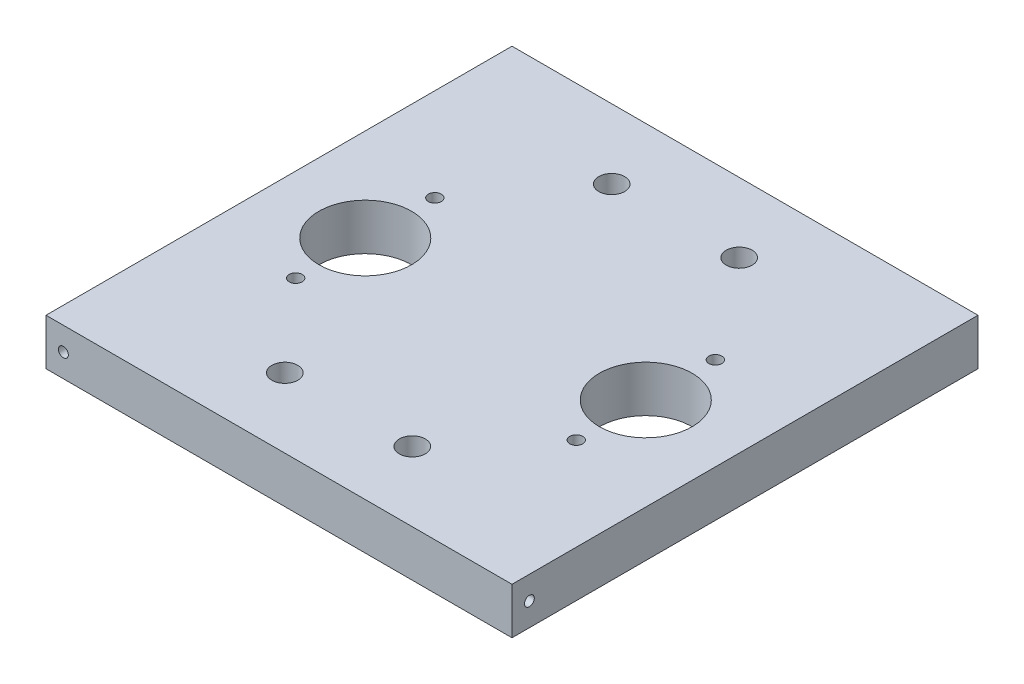
SolidWorks part; units mm, degrees
material "6061-T6 (SS)"
ref_plane "Front" through (0, 0, 0) normal (0, 0, 1) x (1, 0, 0)
ref_plane "Top" through (0, 0, 0) normal (0, 1, 0) x (1, 0, 0)
ref_plane "Right" through (0, 0, 0) normal (1, 0, 0) x (0, 0, -1)
sketch "Sketch1" plane through (0, 0, 0) normal (0, 1, 0) x (1, 0, 0)
  line L1 (0, 0) -> (127.635, 0)
  line L2 (0, 0) -> (0, 127.635)
  line L3 (0, 127.635) -> (127.635, 127.635)
  line L4 (127.635, 0) -> (127.635, 127.635)
  dimension "D1" = 127.635
  dimension "D2" = 127.635
extrude "Main Plate" add sketch "Sketch1" along normal blind 12.7
sketch "Sketch2" plane through (0, 12.7, 0) normal (0, 1, 0) x (1, 0, 0)
  line L0 (0, 127.635) -> (0, 0) construction
  line L1 (127.635, 127.635) -> (0, 127.635) construction
  circle A0 centre (46.355, 108.585) radius 3.556
  dimension "D1" = 7.112
  dimension "D2" = 46.355
  dimension "D3" = 19.05
extrude "U-Bolt Hole" cut sketch "Sketch2" against normal blind 12.7
pattern_linear "U-Bolt Pattern" count 2 spacing 34.925 along (1, 0, 0) count 2 spacing 89.535 along (0, 0, 1) of "U-Bolt Hole"
sketch "Sketch3" plane through (0, 12.7, 0) normal (0, 1, 0) x (1, 0, 0)
  line L0 (0, 127.635) -> (0, 0) construction
  line L1 (0, 0) -> (127.635, 0) construction
  circle A0 centre (25.4, 42.9895) radius 1.778
  dimension "D1" = 3.556
  dimension "D2" = 25.4
  dimension "D3" = 42.9895
extrude "Raptor Bolt Hole" cut sketch "Sketch3" against normal blind 12.7
pattern_linear "Raptor Bolt Pattern" count 2 spacing 38.1 along (0, 0, -1) count 2 spacing 76.835 along (1, 0, 0) of "Raptor Bolt Hole"
sketch "Sketch4" plane through (0, 12.7, 0) normal (0, 1, 0) x (1, 0, 0)
  line L0 (0, 127.635) -> (0, 0) construction
  circle A0 centre (25.4, 62.0395) radius 12.7
  dimension "D1" = 25.4
  dimension "D2" = 19.05
  dimension "D3" = 25.4
extrude "Co2 Cylinder Hole" cut sketch "Sketch4" against normal blind 12.7
pattern_linear "Co2 Pattern" count 2 spacing 76.835 along (1, 0, 0) of "Co2 Cylinder Hole"
sketch "Sketch5" plane through (0, 0, 0) normal (0, 0, 1) x (1, 0, 0)
  line L0 (0, 12.7) -> (0, 0) construction
  line L1 (0, 0) -> (127.635, 0) construction
  circle A0 centre (4.7625, 6.35) radius 1.3526
  dimension "D1" = 2.7051
  dimension "D2" = 4.7625
  dimension "D3" = 6.35
extrude "Frame attachment hole 1" cut sketch "Sketch5" against normal blind 12.7
sketch "Sketch6" plane through (0, 0, 0) normal (-1, 0, 0) x (0, 0, 1)
  line L2 (-127.635, 0) -> (0, 0) construction
  line L3 (-127.635, 12.7) -> (-127.635, 0) construction
  circle A0 centre (-122.8725, 6.35) radius 1.3525
  dimension "D1" = 2.7051
  dimension "D2" = 6.35
  dimension "D3" = 4.7625
extrude "Frame attachment hole 2" cut sketch "Sketch6" against normal blind 12.7
sketch "Sketch7" plane through (0, 0, -127.635) normal (0, 0, -1) x (-1, 0, 0)
  line L2 (-127.635, 0) -> (0, 0) construction
  line L3 (-127.635, 12.7) -> (-127.635, 0) construction
  circle A0 centre (-122.8725, 6.35) radius 1.3525
  dimension "D1" = 2.7051
  dimension "D2" = 6.35
  dimension "D3" = 4.7625
extrude "Frame attachment hole 3" cut sketch "Sketch7" against normal blind 12.7
sketch "Sketch8" plane through (127.635, 0, 0) normal (1, 0, 0) x (0, 0, -1)
  line L2 (0, 0) -> (127.635, 0) construction
  line L3 (0, 12.7) -> (0, 0) construction
  circle A0 centre (4.7625, 6.35) radius 1.3526
  dimension "D1" = 2.7051
  dimension "D2" = 6.35
  dimension "D3" = 4.7625
extrude "Frame attachment hole 4" cut sketch "Sketch8" against normal blind 12.7
